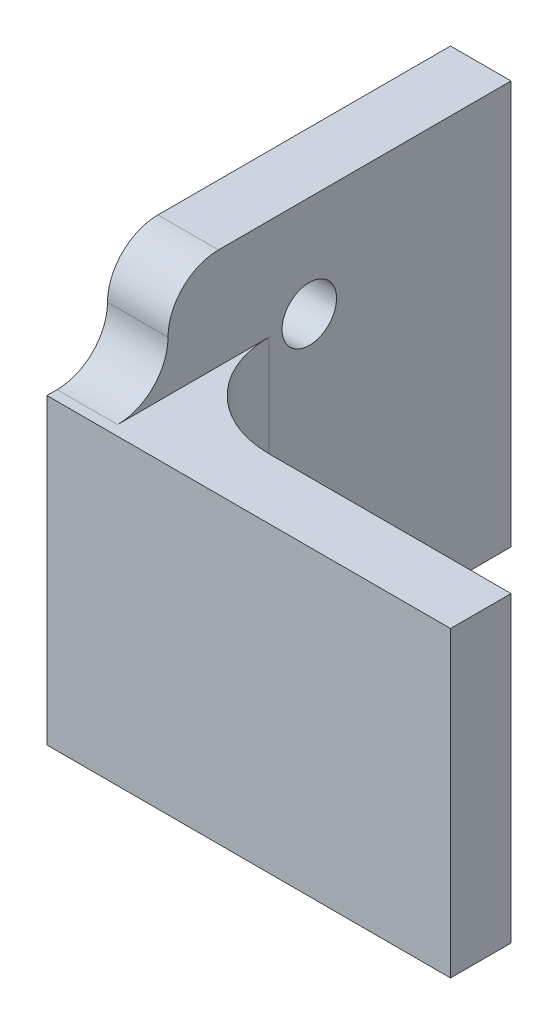
SolidWorks part; units mm, degrees
ref_plane "Front Plane" through (0, 0, 0) normal (0, 0, 1) x (1, 0, 0)
ref_plane "Top Plane" through (0, 0, 0) normal (0, 1, 0) x (1, 0, 0)
ref_plane "Right Plane" through (0, 0, 0) normal (1, 0, 0) x (0, 0, -1)
sketch "Sketch1" plane through (0, 0, 0) normal (0, 1, 0) x (1, 0, 0)
  line L0 (0, 0) -> (0, 17)
  line L1 (0, 17) -> (-3, 17)
  line L2 (-3, 17) -> (-3, -3)
  line L3 (-3, -3) -> (17, -3)
  line L4 (17, -3) -> (17, 0)
  line L5 (17, 0) -> (0, 0)
  dimension "D1" = 20
  dimension "D2" = 3
  dimension "D3" = 20
  dimension "D4" = 3
extrude "Boss-Extrude1" add sketch "Sketch1" along normal blind 20
sketch "Sketch2" plane through (0, 0, 0) normal (1, 0, 0) x (0, 0, -1)
  line L0 (17, 10) -> (-3, 10) construction
  line L1 (17, 20) -> (17, 0) construction
  line L2 (-3, 20) -> (-3, 0) construction
  line L3 (7, 15) -> (7, 5) construction
  point P9 (7, 10)
  point P10 (7, 5)
  point P11 (7, 15)
  point P12 (7, 15)
  point P13 (7, 5)
  dimension "D1" = 10
hole_wizard "Ø2.7 (2.7) Diameter Hole1" positions "Sketch2" profile "Sketch3" hole size "Ø2.7" standard "ANSI Metric"
sketch "Sketch3" plane through (0, 5, -7) normal (0, 1, 0) x (0, 0, -1)
  line L0 (0, 0) -> (0, 15.8112)
  line L1 (0, 15.8112) -> (1.35, 15)
  line L2 (1.35, 15) -> (1.35, 0)
  line L5 (1.35, 0) -> (0, 0)
  line L10 (0, 15.8112) -> (-1.35, 15) construction
  line L11 (0, -6.35) -> (0, 107.95) construction
  dimension "Hole Dia." = 2.7
  dimension "Hole Depth" = 15
  dimension "Drill Angle" = 118
sketch "Sketch4" plane through (0, 20, 0) normal (0, 1, 0) x (1, 0, 0)
  line L1 (17, 0) -> (-3, 0)
  line L2 (17, 0) -> (17, -3)
  line L3 (17, -3) -> (-3, -3)
  line L4 (-3, 0) -> (-3, -3)
  line L5 (17, 0) -> (-3, -3) construction
  line L6 (17, -3) -> (-3, 0) construction
  point P4 (7, -1.5)
extrude "Cut-Extrude1" cut sketch "Sketch4" against normal blind 5
fillet "Fillet2" radius 2.5 2 edges at (-1.5, 15, 0) (-1.5, 20, 0)
fillet "Fillet3" radius 5 1 edges at (0, 7.5, 0)
